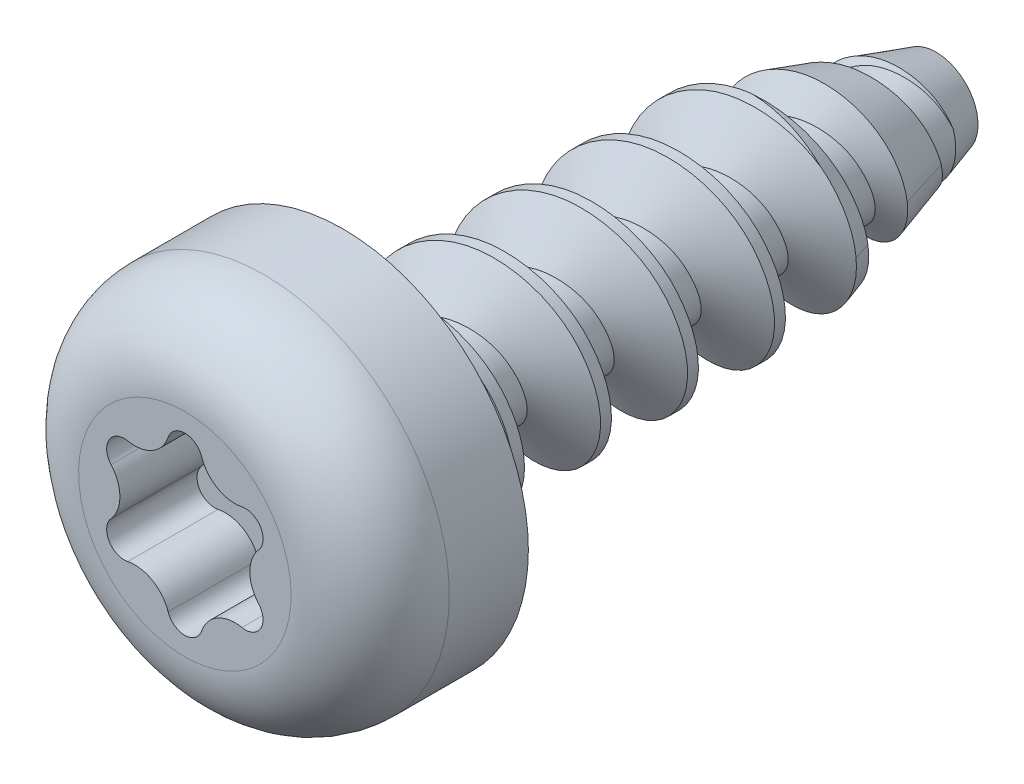
SolidWorks part; units mm, degrees
ref_plane "Front" through (0, 0, 0) normal (0, 0, 1) x (1, 0, 0)
ref_plane "Top" through (0, 0, 0) normal (0, 1, 0) x (1, 0, 0)
ref_plane "Right" through (0, 0, 0) normal (1, 0, 0) x (0, 0, -1)
sketch "Sketch1" plane through (0, 0, 0) normal (0, 0, 1) x (1, 0, 0)
  circle A0 centre (0, 0) radius 0.9375
  dimension "Head Dia" = 1.875
extrude "Extrude3" add sketch "Sketch1" along normal blind 0.8
ref_plane "Plane1" through (0, 0, 0.8) normal (0, 0, 1) x (1, 0, 0)
sketch "Sketch11" plane through (0, 0, 0) normal (1, 0, 0) x (0, 0, -1)
  line L2 (-0.8, 0.9375) -> (-0.8, -0.9375) construction
  line L4 (0, 0.9375) -> (-0.8, 0.9375) construction
  line L5 (-0.4, 0.9375) -> (-0.4, 1.0375)
  line L6 (-0.4, 1.0375) -> (-0.9, 1.0375)
  line L7 (-0.9, 1.0375) -> (-0.9, 0.5375)
  line L8 (-0.9, 0.5375) -> (-0.8, 0.5375)
  line L11 (0, 0) -> (-0.8, 0) construction
  arc A0 (-0.8, 0.5375) -> (-0.4, 0.9375) centre (-0.4, 0.5375) cw
  dimension "D1" = 0.1
  dimension "D2" = 0.1
revolve "Cut-Revolve3" cut sketch "Sketch11" angle 360 about L11
sketch "Sketch14" plane through (0, 0, 0) normal (1, 0, 0) x (0, 0, -1)
  line L0 (0.11, 0.2618) -> (0.2475, 0.5) construction
  line L2 (0.2475, 0.5) -> (0.3025, 0.5)
  line L3 (0.3025, 0.5) -> (0.44, 0.2618) construction
  line L4 (0.44, 0.2618) -> (0.11, 0.2618) construction
  line L5 (0.44, 0.2618) -> (0.55, 0.2618) construction
  line L6 (0.11, 0.2618) -> (0, 0.2618) construction
  line L10 (0, 0.9375) -> (0, -0.9375) construction
  line L11 (0.2475, 0.5) -> (0.11, 0.2618)
  line L12 (0.11, 0.2618) -> (0.44, 0.2618)
  line L13 (0.44, 0.2618) -> (0.3025, 0.5)
  line L14 (0, 0) -> (-0.8, 0) construction
  line L15 (0, 0) -> (-0.8, 0) construction
  point P11 (0.275, 0.5)
  dimension "D1" = 60
  dimension "Pitch" = 0.44
  dimension "D3" = 0.11
  dimension "D4" = 0.055
  dimension "Screw Dia" = 1
ref_plane "Plane2" through (0, 0, -0.275) normal (0, 0, 1) x (1, 0, 0)
sketch "Sketch4" plane through (0, 0, 0) normal (1, 0, 0) x (0, 0, -1)
  line L0 (0, 0) -> (3, 0)
  line L2 (3, -0.2618) -> (0, -0.2618) construction
  line L3 (3, 0) -> (3, 0.2618)
  line L4 (3, 0.2618) -> (0, 0.2618)
  line L5 (0, 0) -> (-0.8, 0) construction
  line L6 (0, 0.2618) -> (0, 0)
  line L7 (3, 0) -> (5.54, 0) construction
  line L8 (0.11, 0.2618) -> (0.44, 0.2618) construction
  point P7 (0, 0.2618)
  dimension "D1" = 2.54
  dimension "Body Length" = 3
revolve "Revolve1" add sketch "Sketch4" angle 360 about L7
sketch "Sketch15" plane through (0, 0, -0.275) normal (0, 0, 1) x (1, 0, 0)
  circle A0 centre (0, 0) radius 0.5
curve "Helix/Spiral1" pitch 0.44 height 0.66 radius 0.5 centre (0, 0, -0.275) axis (0, 0, -1) start towards (0, 1, 0)
sweep "Sweep1" add profiles "Sketch14" path "Helix/Spiral1"
pattern_linear "LPattern3" count 7 spacing 0.44 along (0, 0, -1) count 2 spacing 0.44 along (0, 0, 1) of "Sweep1"
sketch "Sketch13" plane through (0, 0, 0) normal (1, 0, 0) x (0, 0, -1)
  line L0 (3, 0.2118) -> (2.0632, 0.5)
  line L2 (2.0632, 0.5) -> (3, 0.5)
  line L3 (3, 0.5) -> (3, 0.2118) construction
  line L4 (3, 0.2118) -> (3, 0)
  line L5 (0, 0) -> (3, 0) construction
  line L6 (0.2475, 0.5) -> (0.3025, 0.5) construction
  line L7 (3.88, 0) -> (3.88, 0.5)
  line L8 (3.88, 0.5) -> (3, 0.5)
  line L9 (3, 0) -> (3.88, 0)
  dimension "D1" = 17.097
  dimension "D2" = 0.05
  dimension "D3" = 0.88
revolve "Cut-Revolve4" cut sketch "Sketch13" angle 360 about L5
sketch "Sketch12" plane through (0, 0, 0.8) normal (0, 0, 1) x (1, 0, 0)
  line L0 (0, 0) -> (0, 0.443) construction
  line L1 (-0.1643, 0.2845) -> (0, 0)
  line L2 (0, 0) -> (0.1643, 0.2845)
  arc A0 (-0.1643, 0.2845) -> (-0.0844, 0.3822) centre (-0.2533, 0.4388) ccw
  arc A1 (-0.0844, 0.3822) -> (0.0844, 0.3822) centre (0, 0.3539) cw
  arc A2 (0.0844, 0.3822) -> (0.1643, 0.2845) centre (0.2533, 0.4388) ccw
  circle A5 centre (0, 0) radius 0.443 construction
  dimension "D1" = 60
  dimension "M" = 0.8859
  dimension "D2" = 0.0891
  dimension "D3" = 0.1781
ref_axis "Axis1" through (0, 0, 0.8) along (0, 0, -1)
extrude "Cut-Extrude1" cut sketch "Sketch12" against normal blind 0.4571
pattern_circular "CirPattern1" count 6 every 60 about axis through (0, 0, 0.8) along (0, 0, -1) of "Cut-Extrude1"
sketch "Sketch16" plane through (0, 0, 0) normal (1, 0, 0) x (0, 0, -1)
  line L0 (3, 0.5) -> (3, -0.5) construction
  point P0 (-0.8, 0.5375)
  point P1 (0, 0.9375)
  point P3 (2.0632, -0.5)
equation "\"D3@LPattern3\"=\"Pitch@Sketch14\""
equation "\"D1@LPattern3\"=(\"Body Length@Sketch4\"/\"Pitch@Sketch14\")"
equation "\"D1@Cut-Extrude1\"=\"Head Ht@Extrude3\"*2/3.5"
equation "\"D3@Sketch14\" = \"Pitch@Sketch14\"/4"
equation "\"D4@Sketch14\" = \"Pitch@Sketch14\"/8"
equation "\"D4@LPattern3\" = \"D3@LPattern3\""
equation "\"D4@Helix/Spiral1\" = \"Pitch@Sketch14\""
equation "\"D2@Sketch12\" = \"Head Dia@Sketch1\" * .0475"
equation "\"D3@Sketch12\" = \"Head Dia@Sketch1\" * .095"
equation "\"M@Sketch12\" = \"Head Dia@Sketch1\" * 0.4725"
equation "\"D3@Sketch13\" = \"D4@Helix/Spiral1\" * 2"
